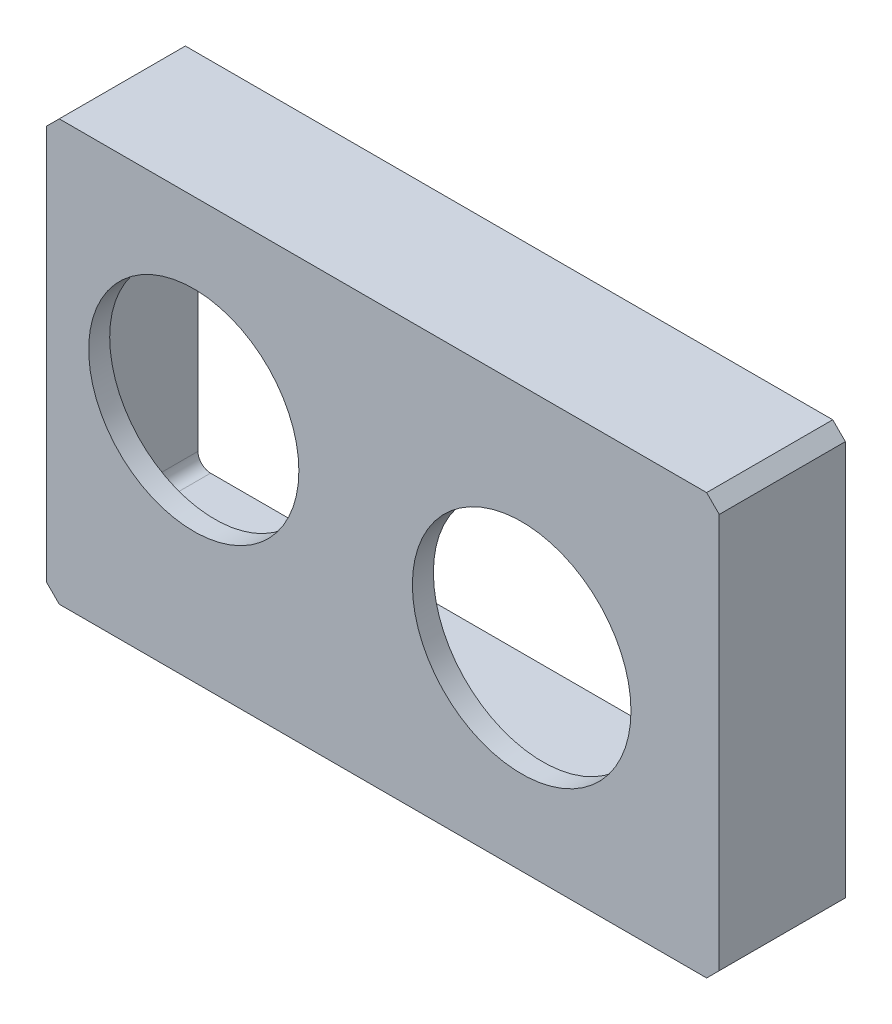
SolidWorks part; units mm, degrees
ref_plane "前视基准面" through (0, 0, 0) normal (0, 0, 1) x (1, 0, 0)
ref_plane "上视基准面" through (0, 0, 0) normal (0, 1, 0) x (1, 0, 0)
ref_plane "右视基准面" through (0, 0, 0) normal (1, 0, 0) x (0, 0, -1)
other "Configuration Table"
sketch "草图1" plane through (0, 0, 0) normal (0, 0, 1) x (1, 0, 0)
  line L2 (0, 0) -> (0, -60)
  line L5 (160, -60) -> (160, 40)
  line L6 (160, 40) -> (68, 40)
  line L8 (68, 40) -> (0, 40)
  line L9 (0, 40) -> (0, 0)
  line L10 (160, -60) -> (0, -60)
  dimension "D1" = 160
  dimension "D4" = 100
extrude "凸台-拉伸1" add sketch "草图1" along normal blind 30
sketch "草图2" plane through (0, 0, 30) normal (0, 0, 1) x (1, 0, 0)
  line L1 (0, 40) -> (0, -60) construction
  line L3 (0, -60) -> (160, -60) construction
  circle A0 centre (35, -4) radius 25
  dimension "D2" = 50
  dimension "D1" = 35
  dimension "D3" = 56
extrude "切除-拉伸1" cut sketch "草图2" against normal through all
sketch "草图4" plane through (0, 0, 0) normal (0, 0, -1) x (-1, 0, 0)
  line L0 (0, 40) -> (0, -60) construction
  line L1 (-6, -45) -> (-146, -45)
  line L2 (-6, -45) -> (-6, 30)
  line L3 (-6, 30) -> (-146, 30)
  line L4 (-146, -45) -> (-146, 30)
  line L5 (-160, 40) -> (0, 40) construction
  circle A0 centre (-113, -13.975) radius 27.5 construction
  dimension "D1" = 55
  dimension "D2" = 75
  dimension "D3" = 140
  dimension "D4" = 6
  dimension "D5" = 10
extrude "切除-拉伸2" cut sketch "草图4" against normal blind 25
sketch "草图5" plane through (0, 0, 25) normal (0, 0, -1) x (-1, 0, 0)
  circle A0 centre (-113, -13.975) radius 26
  dimension "D1" = 52
extrude "切除-拉伸3" cut sketch "草图5" against normal through all
chamfer "倒角3" distance 3 angle 45 4 edges at (160, -60, 15) (160, 40, 15) (0, -60, 15) (0, 40, 15)
fillet "圆角2" radius 3 4 edges at (146, 30, 12.5) (146, -45, 12.5) (6, 30, 12.5) (6, -45, 12.5)
sketch "草图6" plane through (0, 0, 25) normal (0, 0, -1) x (-1, 0, 0)
  line L0 (-9, 30) -> (-143, 30) construction
  line L1 (-66, 30) -> (-146, 30)
  line L2 (-66, 30) -> (-66, 21.5)
  line L3 (-66, 21.5) -> (-146, 21.5)
  line L4 (-146, 30) -> (-146, 21.5)
  line L5 (-146, 27) -> (-146, -42) construction
  dimension "D1" = 80
  dimension "D2" = 8.5
extrude "凸台-拉伸2" add sketch "草图6" along normal up to surface (25 mm away) up to face at (76, -7.5, 0)
